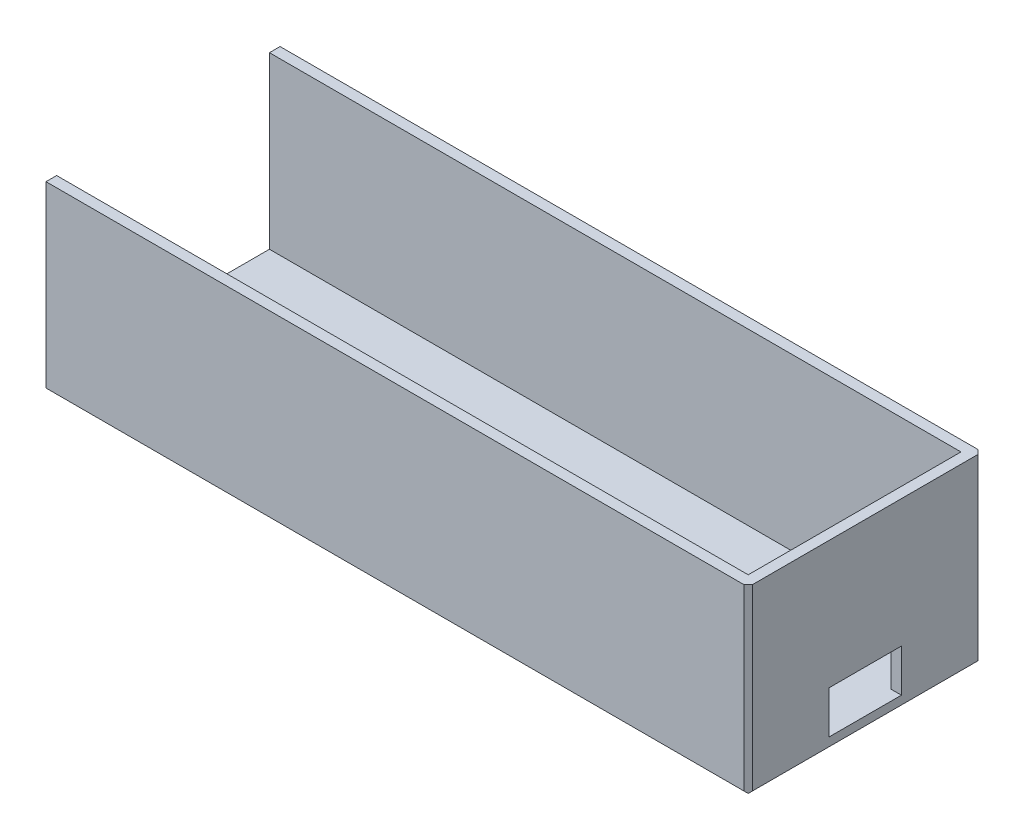
SolidWorks part; units mm, degrees
ref_plane "前视基准面" through (0, 0, 0) normal (0, 0, 1) x (1, 0, 0)
ref_plane "上视基准面" through (0, 0, 0) normal (0, 1, 0) x (1, 0, 0)
ref_plane "右视基准面" through (0, 0, 0) normal (1, 0, 0) x (0, 0, -1)
other "Configuration Table"
sketch "草图1" plane through (0, 0, 0) normal (0, 1, 0) x (1, 0, 0)
  line L0 (70, 0) -> (70, 1)
  line L1 (0, 0) -> (160, 0)
  line L2 (0, 0) -> (0, -50)
  line L3 (0, -50) -> (160, -50)
  line L4 (160, 0) -> (160, -50)
  line L5 (61, 10) -> (61, 0)
  line L6 (79, 10) -> (79, 0)
  line L7 (70, 6) -> (70, 10) construction
  line L8 (70, 6) -> (70, 0) construction
  circle A0 centre (70, 10) radius 4
  arc A1 (79, 10) -> (61, 10) centre (70, 10) ccw
  circle A2 centre (70, 10) radius 9 construction
  dimension "D5" = 8
  dimension "D1" = 50
  dimension "D2" = 160
  dimension "D3" = 10
  dimension "D4" = 70
  dimension "D6" = 5
extrude "凸台-拉伸1" add sketch "草图1" along normal blind 3 contours L4 L1 L2 L3 region at (80, 0, 25)
sketch "草图3" plane through (0, 3, 0) normal (0, 1, 0) x (1, 0, 0)
  line L1 (0, 0) -> (160, 0)
  line L2 (0, 0) -> (0, -50)
  line L3 (0, -50) -> (160, -50)
  line L4 (160, 0) -> (160, -50)
extrude "拉伸-薄壁1" add sketch "草图3" along normal blind 40 and the other way up to surface (3 mm away) separate body thin other way up to face at (80, 0, 25) thin type one direction wall 2.5
sketch "草图4" plane through (-2.5, 0, 0) normal (-1, 0, 0) x (0, 0, 1)
  line L1 (0, 43) -> (50, 43)
  line L2 (0, 43) -> (0, 3)
  line L3 (0, 3) -> (50, 3)
  line L4 (50, 43) -> (50, 3)
extrude "切除-拉伸1" cut sketch "草图4" against normal blind 100
chamfer "倒角1" distance 1 angle 45 4 edges at (162.5, 0, 25) (80, 0, 52.5) (-2.5, 0, 25) (80, 0, -2.5)
chamfer "倒角2" distance 1 angle 45 2 edges at (162.5, 22, -2.5) (162.5, 22, 52.5)
extrude "凸台-拉伸8" add sketch "草图1<4>" along normal blind 5 contours L6 A1 L5 L1 A0 region at (61.2617, 0, -5)
sketch "草图1<4>" plane through (0, 0, 0) normal (0, 1, 0) x (1, 0, 0) same geometry as "草图1"
sketch "草图8" plane through (162.5, 0, 0) normal (1, 0, 0) x (0, 0, -1)
  line L1 (-33.5, 3) -> (-16.5, 3)
  line L2 (-25, 3) -> (-25, 13)
  line L3 (-33.5, 13) -> (-16.5, 13)
  line L4 (-16.5, 3) -> (-16.5, 13)
  line L5 (-33.5, 3) -> (-33.5, 13)
  line L6 (0, 3) -> (-50, 3) construction
  point P8 (0, 0)
  point P9 (0, 0)
  point P10 (0, 0)
  point P11 (0, 0)
  point P12 (0, 0)
  point P13 (-25, 3)
  point P14 (-39, 13)
  point P15 (0, 0)
  point P16 (0, 0)
  point P17 (0, 0)
  point P18 (0, 0)
  point P19 (0, 0)
  point P20 (0, 0)
  point P21 (0, 0)
  dimension "D1" = 10
  dimension "D2" = 17
extrude "切除-拉伸3" cut sketch "草图8" against normal blind 10 contours L1 L4 L3 L2 | L5 L1 L2 L3 region at (162.5, 8, 29.25) region at (162.5, 8, 20.75)
